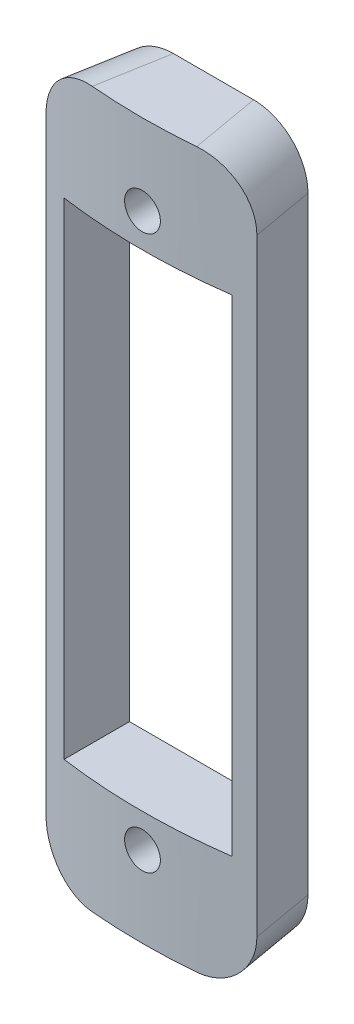
SolidWorks part; units mm, degrees
material "ABS"
ref_plane "Front Plane" through (0, 0, 0) normal (0, 0, 1) x (1, 0, 0)
ref_plane "Top Plane" through (0, 0, 0) normal (0, 1, 0) x (1, 0, 0)
ref_plane "Right Plane" through (0, 0, 0) normal (1, 0, 0) x (0, 0, -1)
sketch "Sketch1" plane through (0, 0, 0) normal (1, 0, 0) x (0, 0, -1)
  line L0 (33.9725, 0) -> (33.9725, 16.293) construction
  line L2 (0, 0) -> (2, 0)
  line L3 (0, 0) -> (0, 40)
  line L4 (0, 40) -> (2, 40)
  line L5 (2, 0) -> (2, 40)
  dimension "D1" = 33.9725
  dimension "D2" = 2
  dimension "D3" = 40
revolve "BULK EXTRUDE" add sketch "Sketch1" angle 20 mid plane about L0
sketch "Sketch2" plane through (0, 0, 0) normal (0, 0, 1) x (1, 0, 0)
  line L0 (0, 0) -> (0, 6.4) construction
  line L1 (-4.7, 33.6) -> (4.7, 33.6)
  line L2 (-4.7, 33.6) -> (-4.7, 6.4)
  line L3 (-4.7, 6.4) -> (4.7, 6.4)
  line L4 (4.7, 33.6) -> (4.7, 6.4)
  line L5 (0, 33.6) -> (0, 35.48) construction
  line L6 (0, 6.4) -> (0, 4.52) construction
  circle A0 centre (0, 4.52) radius 1
  circle A1 centre (0, 35.48) radius 1
  point P7 (-4.7, 20)
  dimension "D4" = 2
  dimension "D1" = 27.2
  dimension "D2" = 9.4
  dimension "D3" = 20
  dimension "D5" = 30.96
extrude "CONNECTOR PASSTHRU" cut sketch "Sketch2" against normal through all both and the other way through all
ref_plane "REAR FLATTENING PLANE" through (0, 0, -2.4857) normal (0, 0, 1) x (1, 0, 0)
sketch "Sketch3" plane through (0, 0, -2.4857) normal (0, 0, 1) x (1, 0, 0)
  line L0 (4.7, 6.4) -> (4.7, 33.6) construction
  line L1 (4.7, 6.4) -> (-4.7, 6.4) construction
  line L2 (-4.7, 33.6) -> (-4.7, 6.4) construction
  line L3 (-4.7, 33.6) -> (4.7, 33.6) construction
  line L4 (-5.552, 0) -> (5.552, 0)
  line L5 (-5.552, 40) -> (-5.552, 0)
  line L6 (5.552, 40) -> (-5.552, 40)
  line L7 (5.552, 0) -> (5.552, 40)
  line L8 (-5.552, 0) -> (5.552, 0)
  line L9 (-5.552, 40) -> (-5.552, 0)
  line L10 (5.552, 40) -> (-5.552, 40)
  line L11 (5.552, 0) -> (5.552, 40)
  line L12 (4.7, 6.4) -> (4.7, 33.6)
  line L13 (4.7, 6.4) -> (-4.7, 6.4)
  line L14 (-4.7, 33.6) -> (-4.7, 6.4)
  line L15 (-4.7, 33.6) -> (4.7, 33.6)
  circle A0 centre (0, 4.52) radius 1 construction
  circle A1 centre (0, 35.48) radius 1 construction
  circle A2 centre (0, 4.52) radius 1
  circle A3 centre (0, 35.48) radius 1
  dimension "D1" = 0
extrude "REAR FLATTENING" add sketch "Sketch3" along normal up to next and the other way blind 1.5
sketch "Sketch4" plane through (5.8096, 0, -1.0244) normal (0.9848, 0, -0.1736) x (-0.1736, 0, -0.9848)
  line L1 (-0.5161, 40) -> (4.8893, 40)
  line L2 (-0.5161, 40) -> (-0.5161, 0)
  line L3 (-0.5161, 0) -> (4.8893, 0)
  line L4 (4.8893, 40) -> (4.8893, 0)
extrude "Cut-Extrude2" cut sketch "Sketch4" along normal through all
sketch "Sketch5" plane through (-5.8096, 0, -1.0244) normal (-0.9848, 0, -0.1736) x (-0.1736, 0, 0.9848)
  line L1 (0.5161, 40) -> (-4.8433, 40)
  line L2 (0.5161, 40) -> (0.5161, 0)
  line L3 (0.5161, 0) -> (-4.8433, 0)
  line L4 (-4.8433, 40) -> (-4.8433, 0)
extrude "Cut-Extrude3" cut sketch "Sketch5" along normal through all
fillet "Fillet1" radius 3 4 edges at (5.5934, 40, -2.2509) (5.5934, 0, -2.2509) (-5.5934, 0, -2.2509) (-5.5934, 40, -2.2509)
